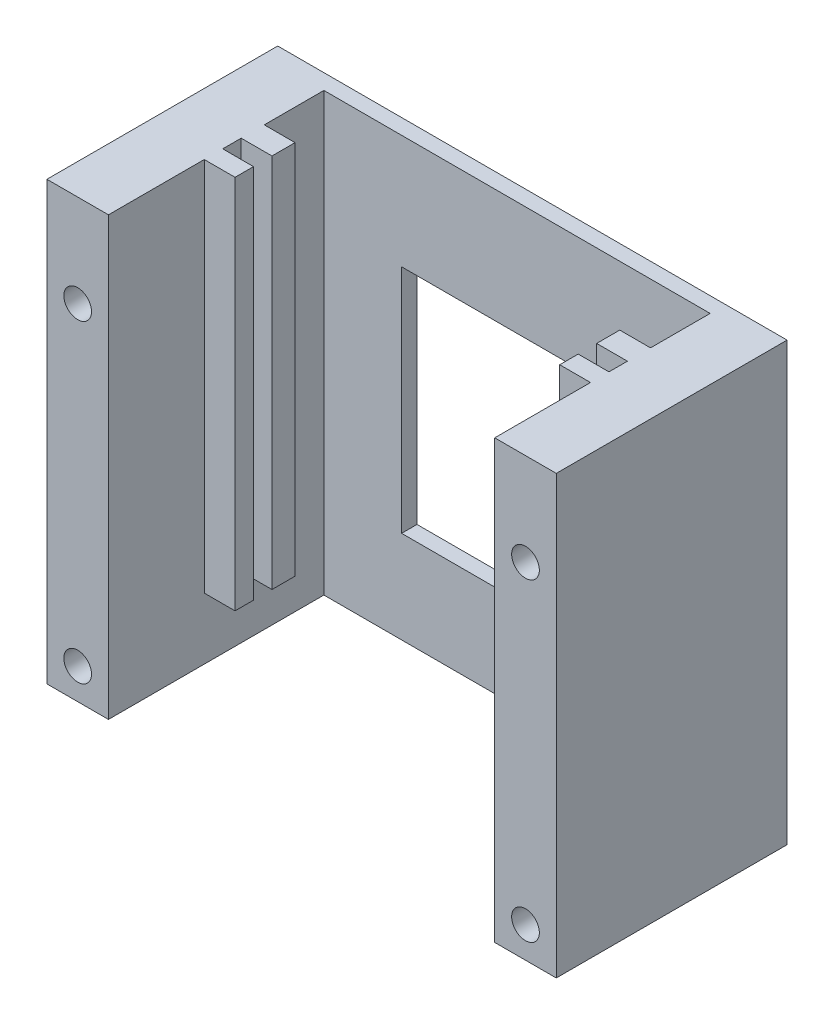
SolidWorks part; units mm, degrees
ref_plane "Plan de face" through (0, 0, 0) normal (0, 0, 1) x (1, 0, 0)
ref_plane "Plan de dessus" through (0, 0, 0) normal (0, 1, 0) x (1, 0, 0)
ref_plane "Plan de droite" through (0, 0, 0) normal (1, 0, 0) x (0, 0, -1)
sketch "Esquisse1" plane through (0, 0, 0) normal (0, 0, 1) x (1, 0, 0)
  line L0 (0, 0) -> (0, -27) construction
  line L1 (0, -27) -> (0, 30) construction
  line L2 (0, 0) -> (25.4165, -15.9375) construction
  line L3 (25.4165, -15.9375) -> (-22.8748, 14.3437) construction
  line L4 (-25.4165, -15.9375) -> (0, 0) construction
  line L5 (0, 0) -> (22.8748, 14.3437) construction
  line L6 (0, 30) -> (25.4165, -15.9375) construction
  line L8 (12.5, -14) -> (-12.5, -14)
  line L9 (12.5, -14) -> (12.5, -17)
  line L10 (12.5, -17) -> (-12.5, -17)
  line L11 (-12.5, -14) -> (-12.5, -17)
  circle A0 centre (0, 0) radius 37
  circle A1 centre (0, 30) radius 1.5
  circle A2 centre (-22.8748, 14.3437) radius 1.5
  circle A3 centre (-25.4165, -15.9375) radius 1.5
  circle A4 centre (0, -27) radius 1.5
  circle A5 centre (25.4165, -15.9375) radius 1.5
  circle A6 centre (22.8748, 14.3437) radius 1.5
  dimension "D1" = 74
  dimension "D11" = 3
  dimension "D12" = 3
  dimension "D13" = 3
  dimension "D14" = 3
  dimension "D15" = 3
  dimension "D16" = 3
  dimension "D2" = 27
  dimension "D3" = 57
  dimension "D4" = 57
  dimension "D5" = 30
  dimension "D6" = 30
  dimension "D7" = 27
  dimension "D8" = 52.5
  dimension "D9" = 52.5
  dimension "D10" = 47.25
  dimension "D17" = 25
  dimension "D18" = 3
  dimension "D19" = 10
  dimension "D20" = 12.5
extrude "Boss.-Extru.1" add sketch "Esquisse1" along normal blind 2
sketch "Esquisse2" plane through (0, 0, 0) normal (0, 0, -1) x (-1, 0, 0)
  line L0 (-16.55, 14.9) -> (-16.55, -13.5)
  line L1 (-12.55, 14.9) -> (12.55, 14.9)
  line L2 (-12.55, 14.9) -> (-12.55, -9.5)
  line L3 (-12.55, -9.5) -> (12.55, -9.5)
  line L4 (12.55, 14.9) -> (12.55, -9.5)
  line L5 (-16.55, -13.5) -> (16.55, -13.5)
  line L6 (16.55, -13.5) -> (16.55, 14.9)
  line L7 (16.55, 14.9) -> (12.55, 14.9)
  line L8 (-16.55, 14.9) -> (-12.55, 14.9)
  point P0 (0, 0)
  dimension "D1" = 25.1
  dimension "D2" = 9.5
  dimension "D3" = 24.4
  dimension "D4" = 4
  dimension "D5" = 4
  dimension "D6" = 4
  dimension "D7" = 12.55
extrude "Boss.-Extru.2" add sketch "Esquisse2" along normal blind 15 contours L8 L0 L5 L6 L7 L4 L3 L2 region at (14.55, 14.4639, 0)
sketch "Esquisse3" plane through (-12.55, 0, 0) normal (1, 0, 0) x (0, 0, -1)
  line L0 (15, 14.9) -> (0, 14.9) construction
  line L1 (10.125, 14.9) -> (8.625, 14.9)
  line L2 (10.125, 14.9) -> (10.125, -13.5)
  line L3 (10.125, -13.5) -> (8.625, -13.5)
  line L4 (8.625, 14.9) -> (8.625, -13.5)
  line L5 (15, -13.5) -> (0, -13.5) construction
  line L6 (0, 14.9) -> (7.5, 14.9) construction
  line L8 (6.225, 14.9) -> (7.425, 14.9)
  line L9 (6.225, 14.9) -> (6.225, -13.5)
  line L10 (6.225, -13.5) -> (7.425, -13.5)
  line L11 (7.425, 14.9) -> (7.425, -13.5)
  line L12 (8, 14.9) -> (8, -13.5) construction
  dimension "D1" = 1.5
  dimension "D2" = 0.625
  dimension "D3" = 1.2
  dimension "D4" = 1.2
  dimension "D5" = 0.575
  dimension "D6" = 0.5
extrude "Boss.-Extru.3" add sketch "Esquisse3" along normal blind 2 contours L11 L10 L9 L8 | L2 L3 L4 L1
sketch "Esquisse5" plane through (12.55, 0, 0) normal (-1, 0, 0) x (0, 0, 1)
  line L1 (-10.125, 14.9) -> (-8.625, 14.9)
  line L2 (-10.125, 14.9) -> (-10.125, -9.5)
  line L3 (-10.125, -9.5) -> (-8.625, -9.5)
  line L4 (-8.625, 14.9) -> (-8.625, -9.5)
  line L5 (-7.425, 14.9) -> (-6.225, 14.9)
  line L6 (-7.425, 14.9) -> (-7.425, -9.5)
  line L7 (-7.425, -9.5) -> (-6.225, -9.5)
  line L8 (-6.225, 14.9) -> (-6.225, -9.5)
extrude "Boss.-Extru.4" add sketch "Esquisse5" along normal blind 2
sketch "Esquisse7" plane through (0, 0, -15) normal (0, 0, -1) x (-1, 0, 0)
  line L1 (-16.55, 14.9) -> (16.55, 14.9)
  line L2 (-16.55, 14.9) -> (-16.55, -13.5)
  line L3 (-16.55, -13.5) -> (16.55, -13.5)
  line L4 (16.55, 14.9) -> (16.55, -13.5)
extrude "Boss.-Extru.5" add sketch "Esquisse7" against normal blind 1
sketch "Esquisse8" plane through (0, 0, -15) normal (0, 0, -1) x (-1, 0, 0)
  line L1 (-7.5, 7.5) -> (7.5, 7.5)
  line L2 (-7.5, 7.5) -> (-7.5, -7.5)
  line L3 (-7.5, -7.5) -> (7.5, -7.5)
  line L4 (7.5, 7.5) -> (7.5, -7.5)
  line L5 (-7.5, 7.5) -> (7.5, -7.5) construction
  line L6 (-7.5, -7.5) -> (7.5, 7.5) construction
  point P0 (0, 0)
  dimension "D1" = 15
  dimension "D2" = 15
extrude "Enlèv. mat.-Extru.1" cut sketch "Esquisse8" against normal blind 3 contours L3 L4 L1 L2
sketch "Esquisse9" plane through (0, -13.5, 0) normal (0, -1, 0) x (1, 0, 0)
  line L0 (16.55, 0) -> (-16.55, 0) construction
  line L1 (-10.5, -4.4) -> (10.5, -4.4)
  line L2 (-10.5, -4.4) -> (-10.5, -6.9)
  line L3 (-10.5, -6.9) -> (10.5, -6.9)
  line L4 (10.5, -4.4) -> (10.5, -6.9)
  line L6 (10.5, -4.4) -> (10.5, 0) construction
  line L7 (10.5, 0) -> (-10.5, 0) construction
  line L8 (-10.5, 0) -> (-10.5, -4.4) construction
  point P6 (0, -4.4)
  dimension "D1" = 21
  dimension "D2" = 2.5
  dimension "D3" = 4.4
  dimension "D4" = 0
extrude "Enlèv. mat.-Extru.2" cut sketch "Esquisse9" against normal up to surface (4 mm away) contours L1 L4 L3 L2 up to face at (0, -9.5, -7.88)
sketch "Esquisse10" plane through (0, 0, 2) normal (0, 0, 1) x (1, 0, 0)
  line L0 (16.55, -13.5) -> (-16.55, -13.5) construction
  line L1 (-16.55, -13.5) -> (-16.55, 14.9) construction
  line L2 (16.55, 14.9) -> (16.55, -13.5) construction
  line L3 (16.55, 14.9) -> (12.55, 14.9) construction
  line L4 (-16.55, 14.9) -> (-12.55, 14.9) construction
  circle A0 centre (-14.55, 8.9) radius 0.9
  circle A1 centre (-14.55, -11.5) radius 0.9
  circle A2 centre (14.55, -11.5) radius 0.9
  circle A3 centre (14.55, 8.9) radius 0.9
  dimension "D1" = 1.8
  dimension "D2" = 1.8
  dimension "D3" = 1.8
  dimension "D4" = 1.8
  dimension "D5" = 2
  dimension "D6" = 2
  dimension "D7" = 2
  dimension "D8" = 2
  dimension "D9" = 2
  dimension "D10" = 6
  dimension "D11" = 6
  dimension "D12" = 2
extrude "Enlèv. mat.-Extru.3" cut sketch "Esquisse10" against normal blind 9
sketch "Esquisse11" plane through (0, 0, 2) normal (0, 0, 1) x (1, 0, 0)
  circle A0 centre (0, 0) radius 37
extrude "Enlèv. mat.-Extru.4" cut sketch "Esquisse11" against normal blind 2
sketch "Sketch1" plane through (0, 0, -15) normal (0, 0, -1) x (-1, 0, 0)
  line L0 (7.5, 7.5) -> (-7.5, -7.5)
  line L1 (-7.5, -7.5) -> (-7.5, 7.5)
  line L2 (-7.5, 7.5) -> (7.5, -7.5)
  point P4 (0, 0)
sketch "Esquisse12" plane through (0, 0, 0) normal (0, 1, 0) x (1, 0, 0)
  line L0 (16.55, 0) -> (-16.55, 0) construction
  line L1 (-12.55, 0) -> (12.55, 0)
  line L2 (-12.55, 0) -> (-12.55, 14)
  line L3 (-12.55, 14) -> (12.55, 14)
  line L4 (12.55, 0) -> (12.55, 14)
  line L5 (16.55, 15) -> (16.55, 0) construction
  line L6 (-16.55, 15) -> (-16.55, 0) construction
  line L7 (16.55, 15) -> (-16.55, 15) construction
  dimension "D1" = 4
  dimension "D2" = 4
  dimension "D3" = 1
sketch "Esquisse13" plane through (0, -13.5, 0) normal (0, -1, 0) x (1, 0, 0)
  line L1 (-12.55, 0) -> (12.55, 0)
  line L2 (-12.55, 0) -> (-12.55, -14)
  line L3 (-12.55, -14) -> (12.55, -14)
  line L4 (12.55, 0) -> (12.55, -14)
extrude "Enlèv. mat.-Extru.5" cut sketch "Esquisse13" against normal blind 4
